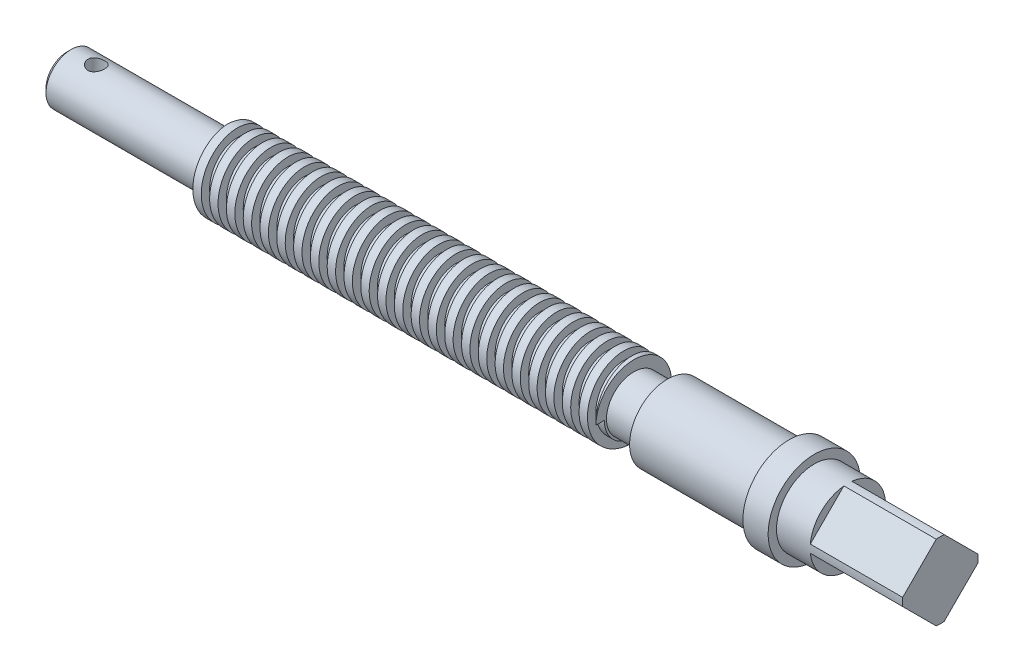
SolidWorks part; units mm, degrees
material "45"
ref_plane "前视基准面" through (0, 0, 0) normal (0, 0, 1) x (1, 0, 0)
ref_plane "上视基准面" through (0, 0, 0) normal (0, 1, 0) x (1, 0, 0)
ref_plane "右视基准面" through (0, 0, 0) normal (1, 0, 0) x (0, 0, -1)
sketch "草图1" plane through (0, 0, 0) normal (0, 0, 1) x (1, 0, 0)
  line L0 (-61.6861, 0) -> (310.1895, 0) construction
  line L1 (0, 0) -> (0, 6)
  line L2 (0, 6) -> (38, 6)
  line L3 (38, 6) -> (38, 9)
  line L4 (38, 9) -> (135, 9)
  line L5 (135, 9) -> (135, 6.5)
  line L6 (135, 6.5) -> (143, 6.5)
  line L7 (143, 6.5) -> (143, 9)
  line L8 (143, 9) -> (172, 9)
  line L9 (172, 9) -> (172, 11)
  line L10 (172, 11) -> (178, 11)
  line L11 (178, 11) -> (178, 9)
  line L12 (178, 9) -> (208, 9)
  line L13 (208, 9) -> (208, 0)
  line L14 (0, 0) -> (208, 0)
  dimension "D1" = 208
  dimension "D2" = 38
  dimension "D3" = 8
  dimension "D4" = 135
  dimension "D5" = 30
  dimension "D6" = 172
  dimension "D7" = 12
  dimension "D8" = 18
  dimension "D9" = 13
  dimension "D10" = 22
revolve "旋转1" add sketch "草图1" angle 360 about L0
chamfer "倒角1" distance 1 angle 45 1 edges at (0, 0, 6)
sketch "草图2" plane through (208, 0, 0) normal (1, 0, 0) x (0, 0, -1)
  line L0 (0, 0) -> (-8.9413, 8.9413) construction
  line L1 (0, 0) -> (8.2715, 8.2715) construction
  line L2 (0, 0) -> (12.8724, 0) construction
  line L3 (-9.8995, 0) -> (0, 9.8995)
  line L4 (0, 9.8995) -> (9.8995, 0)
  line L5 (9.8995, 0) -> (0, -9.8995)
  line L6 (0, -9.8995) -> (-9.8995, 0)
  dimension "D1" = 45
  dimension "D3" = 14
extrude "切除-拉伸1" cut sketch "草图2" against normal blind 22 flip side to cut
sketch "草图3" plane through (0, 0, 0) normal (0, 1, 0) x (1, 0, 0)
  line L0 (-61.6861, 0) -> (310.1895, 0) construction
  line L1 (-61.6861, 0) -> (310.1895, 0) construction
  line L2 (172, 11) -> (172, -11) construction
  circle A0 centre (7, 0) radius 2
  dimension "D1" = 4
  dimension "D2" = 165
extrude "切除-拉伸2" cut sketch "草图3" against normal through all and the other way through all
sketch "草图4" plane through (38, 0, 0) normal (-1, 0, 0) x (0, 0, 1)
  circle A1 centre (0, 0) radius 9
  circle A2 centre (0, 0) radius 9
  dimension "D1" = 0
curve "螺旋线/涡状线1" pitch 4 height 97 turns 24.25
sketch "草图5" plane through (0, 0, 0) normal (0, 1, 0) x (1, 0, 0)
  line L0 (37, -7) -> (37, -9)
  line L1 (37, -7) -> (39, -7)
  line L2 (37, -9) -> (39, -9)
  line L3 (39, -7) -> (39, -9)
  line L4 (38, 9) -> (38, -9) construction
  line L5 (38, -9) -> (135, -9) construction
  dimension "D1" = 2
  dimension "D2" = 2
  dimension "D3" = 1
sweep "切除-扫描1" cut profiles "草图5" path "螺旋线/涡状线1"
